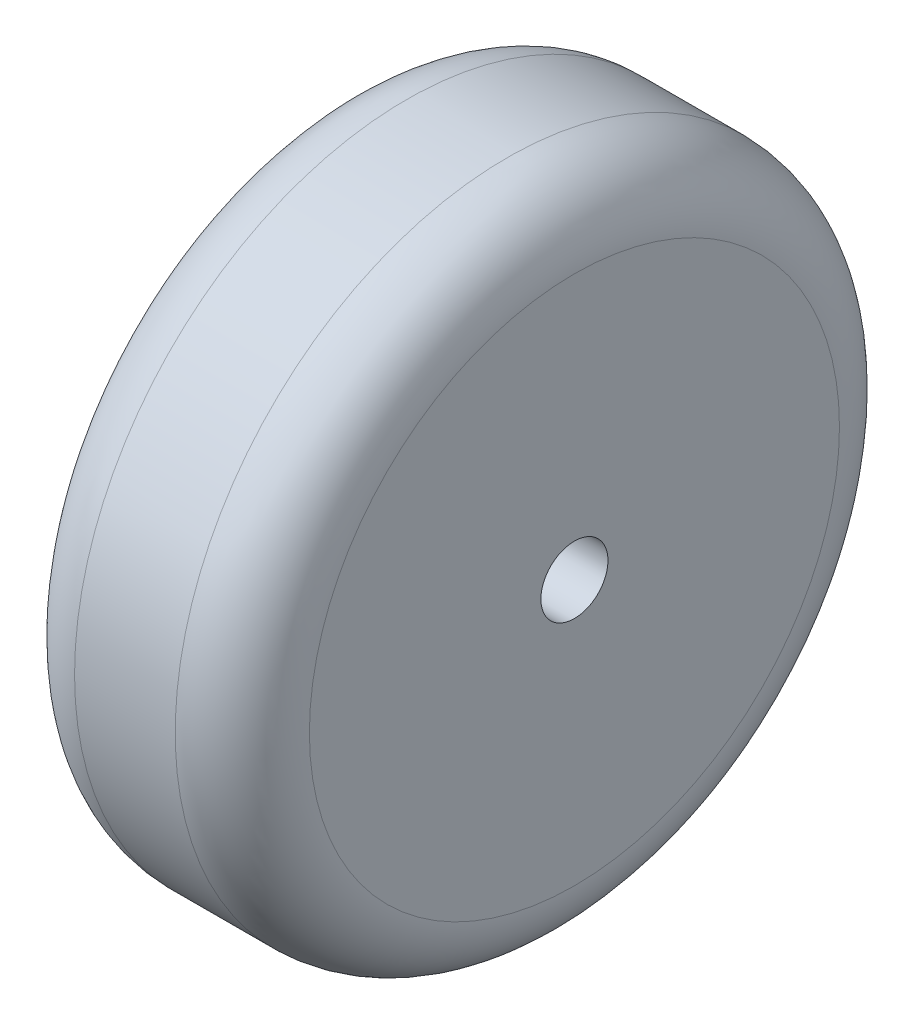
SolidWorks part; units mm, degrees
material "POLIURETANICHE (11671)"
ref_plane "Piano frontale" through (0, 0, 0) normal (0, 0, 1) x (1, 0, 0)
ref_plane "Piano superiore" through (0, 0, 0) normal (0, 1, 0) x (1, 0, 0)
ref_plane "Piano destro" through (0, 0, 0) normal (1, 0, 0) x (0, 0, -1)
other "Centro di massa"
sketch "Schizzo1" plane through (0, 0, 0) normal (0, 0, 1) x (1, 0, 0)
  line L0 (45, 0) -> (-45, 0) construction
  line L9 (-35, 99) -> (35, 99)
  line L10 (35, 99) -> (35, 10)
  line L11 (35, 10) -> (15.51, 10)
  line L12 (15.51, 10) -> (15.51, 17.5)
  line L13 (15.51, 17.5) -> (4.51, 17.5)
  line L14 (4.51, 17.5) -> (4.51, 32.5)
  line L17 (4.51, 32.5) -> (-28.39, 32.5)
  line L18 (-28.39, 32.5) -> (-28.39, 56.75)
  line L19 (-28.39, 56.75) -> (-35, 56.75)
  line L20 (-35, 56.75) -> (-35, 99)
  point P4 (0, 0)
  point P8 (0, 99)
  dimension "D1" = 90
  dimension "D2" = 70
  dimension "D3" = 19.49
  dimension "D4" = 11
  dimension "D5" = 32.9
  dimension "D6" = 20
  dimension "D7" = 35
  dimension "D8" = 65
  dimension "D9" = 113.5
  dimension "D10" = 198
revolve "Rivoluzione1" add sketch "Schizzo1" angle 360 about L0
fillet "Raccordo1" radius 20 2 edges at (35, 0, -99) (-35, 0, -99)
ref_axis "Assi1" through (-125.9579, 0, 0) along (1, 0, 0)
ref_plane "Piano1" through (0, 0, 0) normal (1, 0, 0) x (0, 0, -1)
sketch "Schizzo2" plane through (-35, 0, 0) normal (-1, 0, 0) x (0, 0, 1)
  line L0 (-5, 66.5293) -> (5, 66.5293)
  line L1 (-5, 66.5293) -> (-5, 56.5293)
  line L2 (5, 66.5293) -> (5, 56.5293)
  line L3 (0, 66.5293) -> (0, 0) construction
  circle A0 centre (0, 0) radius 56.75 construction
  circle A1 centre (0, 0) radius 56.75 construction
  arc A2 (5, 56.5293) -> (-5, 56.5293) centre (0, 0) ccw
  point P3 (0, 66.5293)
  dimension "D1" = 10
  dimension "D2" = 10
extrude "Estrusione-Estrusione1" add sketch "Schizzo2" along normal blind 1
other "Punto di riferimento centro di massa1"
